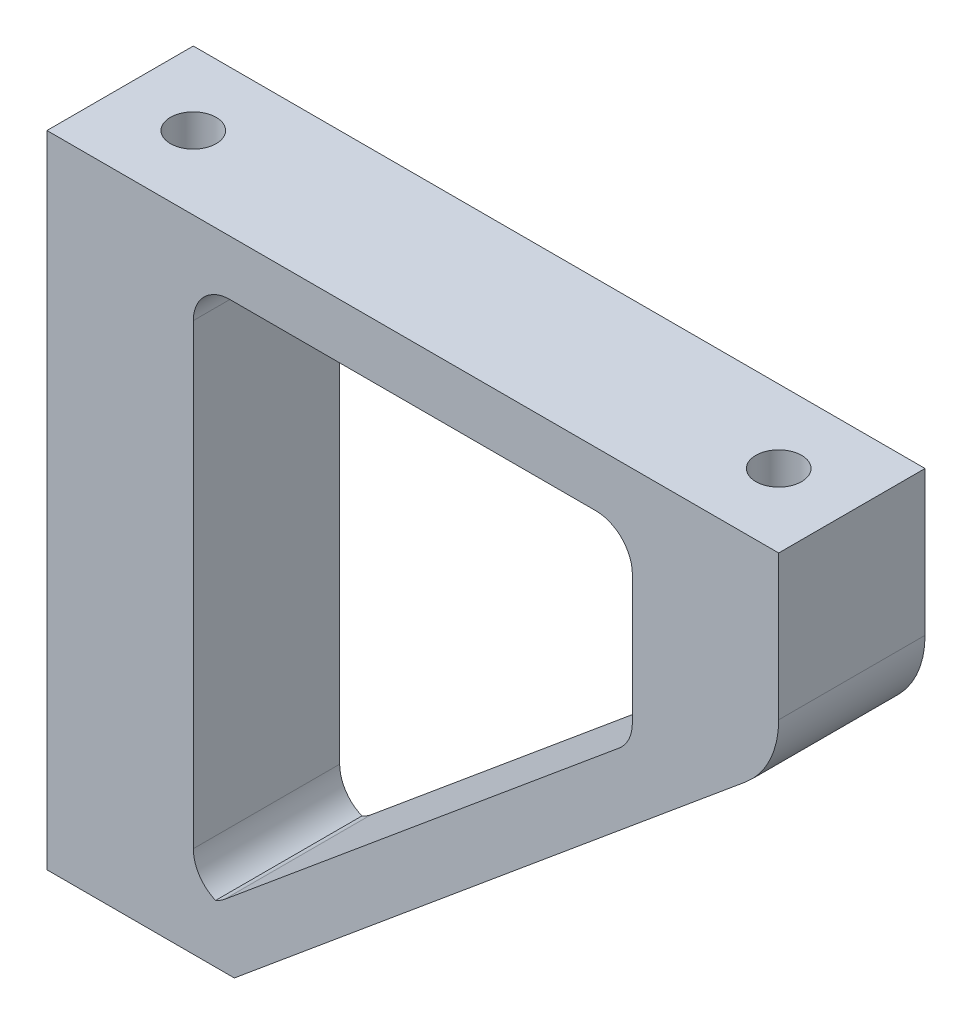
SolidWorks part; units mm, degrees
ref_plane "Спереди" through (0, 0, 0) normal (0, 0, 1) x (1, 0, 0)
ref_plane "Сверху" through (0, 0, 0) normal (0, 1, 0) x (1, 0, 0)
ref_plane "Справа" through (0, 0, 0) normal (1, 0, 0) x (0, 0, -1)
sketch "Эскиз1" plane through (0, 0, 0) normal (0, 0, 1) x (1, 0, 0)
  line L0 (-20, 17.5) -> (-20, -17.5)
  line L1 (-20, -17.5) -> (-9.7574, -17.5)
  line L2 (-9.7574, -17.5) -> (20, 7.2574)
  line L3 (20, 7.2574) -> (20, 17.5)
  line L4 (20, 17.5) -> (-20, 17.5)
  line L5 (-12, 14.5) -> (-12, -14.5)
  line L6 (-12, -14.5) -> (-10.8421, -14.5)
  line L7 (-10.8421, -14.5) -> (12, 4.5041)
  line L8 (12, 4.5041) -> (12, 14.5)
  line L9 (12, 14.5) -> (-12, 14.5)
  line L10 (-16, 17.5) -> (-16, -17.5) construction
  line L11 (-12, 14.5) -> (-20, 14.5) construction
  line L12 (12, 14.5) -> (20, 14.5) construction
  line L13 (16, 17.5) -> (16, 3.9295) construction
  point P1 (0, 17.5)
  point P6 (-20, 0)
  point P9 (0, 14.5)
  point P14 (-12, 0)
  point P16 (-16, 14.5)
  point P22 (16, 14.5)
  dimension "D1" = 8
  dimension "D2" = 3
  dimension "D3" = 35
  dimension "D4" = 3
  dimension "D5" = 32
extrude "тело" add sketch "Эскиз1" along normal blind 8
fillet "Скругление1" radius 2 5 edges at (-10.8421, -14.5, 4) (12, 4.5041, 4) (12, 14.5, 4) (-12, 14.5, 4) (-12, -14.5, 4)
sketch "Эскиз5" plane through (0, -17.5, 0) normal (0, -1, 0) x (1, 0, 0)
  line L0 (-20, 0) -> (-9.7574, 0) construction
  line L1 (-20, 8) -> (-12, 8) construction
  line L2 (-20, 8) -> (-20, 0) construction
  line L3 (-20, 0) -> (-12, 0) construction
  line L4 (-12, 8) -> (-12, 0) construction
  line L5 (-20, 4) -> (-12, 4) construction
  circle A0 centre (-16, 4) radius 1.25
  dimension "D1" = 2.5
extrude "отверстие под шуруп снизу" cut sketch "Эскиз5" against normal through all
sketch "Эскиз6" plane through (0, 17.5, 0) normal (0, 1, 0) x (1, 0, 0)
  line L0 (20, -8) -> (-20, -8) construction
  line L1 (20, 0) -> (12, 0) construction
  line L2 (20, 0) -> (20, -8) construction
  line L3 (20, -8) -> (12, -8) construction
  line L4 (12, 0) -> (12, -8) construction
  line L5 (12, -4) -> (20, -4) construction
  circle A0 centre (16, -4) radius 1.25
  dimension "D1" = 2.5
extrude "отверстие под шуруп сверху" cut sketch "Эскиз6" against normal blind 10
sketch "Эскиз7" [suppressed] plane through (0, 0, 0) normal (0, 0, 1) x (1, 0, 0)
  line L0 (-62.3538, 18.3615) -> (-62.3538, -16.6385)
  line L1 (-62.3538, -16.6385) -> (-51.5846, -16.6385)
  line L2 (-51.5846, -16.6385) -> (-32.8829, 7.5923)
  line L3 (-32.8829, 7.5923) -> (-32.8829, 18.3615)
  line L4 (-32.8829, 18.3615) -> (-62.3538, 18.3615)
  line L5 (-58.5846, 15.1308) -> (-58.5846, -12.1154)
  line L6 (-58.5846, -12.1154) -> (-53.0893, -12.1154)
  line L7 (-53.0893, -12.1154) -> (-39.2792, 5.7776)
  line L8 (-39.2792, 5.7776) -> (-39.2792, 15.1308)
  line L9 (-39.2792, 15.1308) -> (-58.5846, 15.1308)
  line L10 (-58.5846, 15.1308) -> (-62.3538, 15.1308) construction
  line L11 (-39.2792, 15.1308) -> (-32.8829, 15.1308) construction
  line L12 (-60.4692, 18.3615) -> (-60.4692, -16.6385) construction
  line L13 (-36.0811, 18.3615) -> (-36.0811, 3.4486) construction
  point P14 (-60.4692, 15.1308)
  point P17 (-36.0811, 15.1308)
  dimension "D1" = 35
fillet "Скругление2" radius 5 1 edges at (20, 7.2574, 4)
